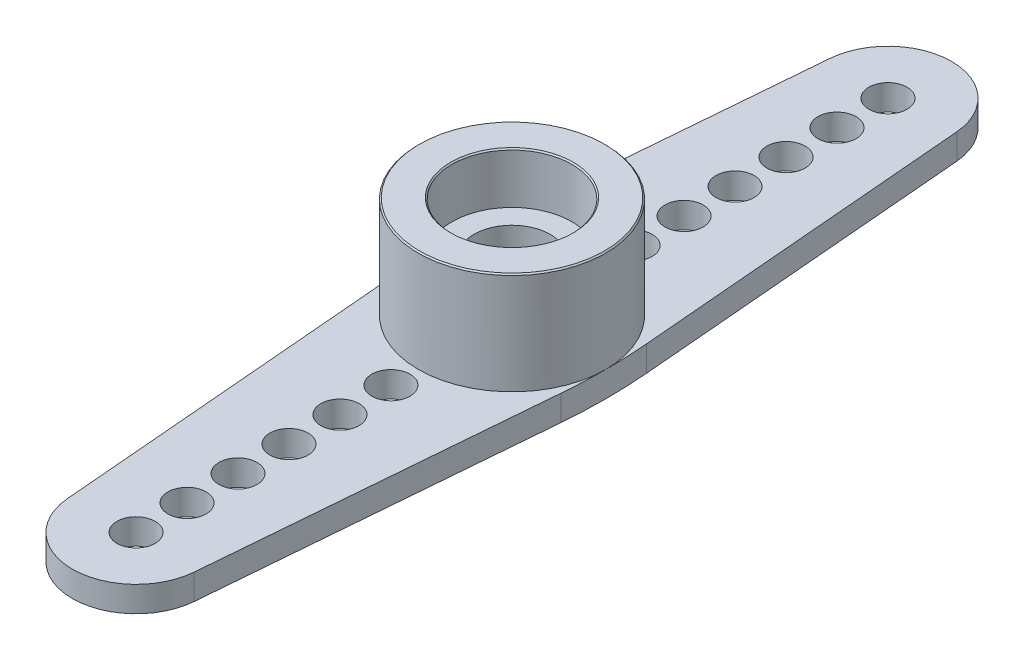
SolidWorks part; units mm, degrees
ref_plane "Ön Düzlem" through (0, 0, 0) normal (0, 0, 1) x (1, 0, 0)
ref_plane "Üst Düzlem" through (0, 0, 0) normal (0, 1, 0) x (1, 0, 0)
ref_plane "Sağ Düzlem" through (0, 0, 0) normal (1, 0, 0) x (0, 0, -1)
sketch "Sketch1" plane through (0, 0, 0) normal (0, 1, 0) x (1, 0, 0)
  line L0 (0, 14.75) -> (0, -14.75) construction
  line L1 (2.5, 14.75) -> (2.5, -14.75) construction
  line L2 (-2.5, 14.75) -> (-2.5, -14.75) construction
  line L3 (-2.4912, 14.9596) -> (-3.6089, 1.677)
  line L4 (-3.6089, -1.677) -> (-2.4912, -14.9596)
  line L5 (0, 2.3316) -> (0, -2.9182) construction
  line L6 (0, -14.75) -> (0, -19.3684) construction
  line L7 (2.4912, 14.9596) -> (3.6089, 1.677)
  line L8 (3.6089, -1.677) -> (2.4912, -14.9596)
  line L9 (-3.6793, 0) -> (8.7348, 0) construction
  arc A0 (2.5, 14.75) -> (-2.5, 14.75) centre (0, 14.75) ccw construction
  arc A1 (-2.5, -14.75) -> (2.5, -14.75) centre (0, -14.75) ccw construction
  arc A2 (-2.4912, 14.9596) -> (2.4912, 14.9596) centre (0, 14.75) cw
  arc A3 (-2.5, -14.75) -> (2.5, -14.75) centre (0, -14.75) ccw
  circle A4 centre (0, 14.75) radius 0.75
  arc A5 (3.6089, -1.677) -> (3.6089, 1.677) centre (-16.3207, 0) ccw
  arc A6 (-3.6089, -1.677) -> (-3.6089, 1.677) centre (16.3207, 0) cw
  circle A7 centre (0, 0) radius 3.6793 construction
  circle A8 centre (0, 12.75) radius 0.75
  circle A9 centre (0, 10.75) radius 0.75
  circle A10 centre (0, 8.75) radius 0.75
  circle A11 centre (0, 6.75) radius 0.75
  circle A12 centre (0, 4.75) radius 0.75
  circle A13 centre (0, -4.75) radius 0.75
  circle A14 centre (0, -6.75) radius 0.75
  circle A15 centre (0, -8.75) radius 0.75
  circle A16 centre (0, -10.75) radius 0.75
  circle A17 centre (0, -12.75) radius 0.75
  circle A18 centre (0, -14.75) radius 0.75
  circle A19 centre (0, 0) radius 0.75
  point P2 (0, 0)
  point P25 (3.75, 0)
  point P28 (-3.75, 0)
  dimension "D1" = 2.5
  dimension "D4" = 1.5
  dimension "D5" = 20
  dimension "D7" = 1.5
  dimension "D2" = 29.5
  dimension "D3" = 3.75
  dimension "D6" = 6
extrude "Boss-Extrude2" add sketch "Sketch1" along normal blind 1 contours A6 L4 A3 L8 A5 L7 A2 L3 A19 A17 A15 A13 A12 A11 A10 A9 A8 A4 A14 A16 A18 region at (0, 0, -16.8972)
sketch "Sketch2" plane through (0, 0, 0) normal (0, -1, 0) x (1, 0, 0)
  circle A0 centre (0, 0) radius 1.5
  circle A1 centre (0, 0) radius 3.6793 construction
  circle A2 centre (0, 0) radius 3.6793
  dimension "D1" = 3
extrude "Boss-Extrude6" add sketch "Sketch2" against normal blind 5 contours A0 | A2
sketch "Sketch4" plane through (0, 0, 0) normal (0, -1, 0) x (1, 0, 0)
  circle A0 centre (0, 0) radius 0.75 construction
  circle A1 centre (0, 0) radius 0.75
extrude "Boss-Extrude7" add sketch "Sketch4" against normal up to surface (1 mm away) up to face at (0, 1, 0.75)
sketch "Sketch5" plane through (0, 0, 0) normal (0, -1, 0) x (1, 0, 0)
  circle A0 centre (0, 0) radius 1.5
  dimension "D1" = 3
extrude "Cut-Extrude2" cut sketch "Sketch5" against normal blind 0.5
extrude "Cut-Extrude3" cut sketch "Sketch1<5>" along normal through all contours A19
sketch "Sketch1<5>" plane through (0, 0, 0) normal (0, 1, 0) x (1, 0, 0) same geometry as "Sketch1"
sketch "Sketch6" plane through (0, 5, 0) normal (0, 1, 0) x (1, 0, 0)
  circle A0 centre (0, 0) radius 2.355
  dimension "D1" = 4.71
extrude "Cut-Extrude4" cut sketch "Sketch6" against normal blind 2
chamfer "Chamfer1" distance 0.05 angle 45 2 edges at (0, 5, -3.6793) (0, 5, 2.355)
